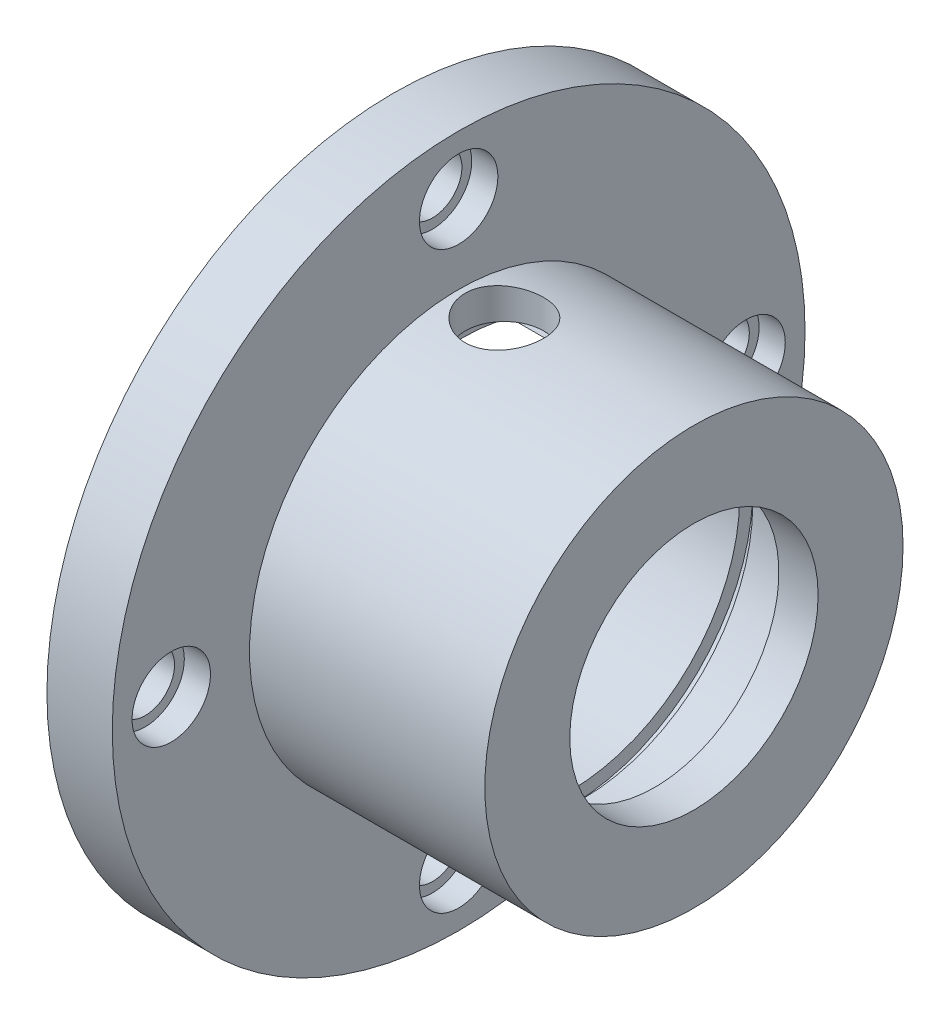
SolidWorks part; units mm, degrees
ref_plane "Front Plane" through (0, 0, 0) normal (0, 0, 1) x (1, 0, 0)
ref_plane "Top Plane" through (0, 0, 0) normal (0, 1, 0) x (1, 0, 0)
ref_plane "Right Plane" through (0, 0, 0) normal (1, 0, 0) x (0, 0, -1)
sketch "Sketch1" plane through (0, 0, 0) normal (1, 0, 0) x (0, 0, -1)
  circle A0 centre (0, 0) radius 26.5
  circle A2 centre (0, -21.9877) radius 2.25
  circle A3 centre (-21.9877, 0) radius 2.25
  circle A4 centre (0, 21.9877) radius 2.25
  circle A5 centre (21.9877, 0) radius 2.25
  point P14 (0, 0)
  dimension "D1" = 53
  dimension "D2" = 4
  dimension "D3" = 4.5
extrude "Boss-Extrude1" add sketch "Sketch1" along normal mid plane 23
sketch "Sketch2" plane through (11.5, 0, 0) normal (1, 0, 0) x (0, 0, -1)
  circle A0 centre (0, 0) radius 16
  circle A1 centre (0, 0) radius 26.5
  circle M3 centre (0, 21.9877) radius 2.25
  circle M4 centre (0, -21.9877) radius 2.25
  circle M5 centre (0, 0) radius 26.5
  circle M6 centre (-21.9877, 0) radius 2.25
  circle M7 centre (21.9877, 0) radius 2.25
  dimension "D1" = 53
  dimension "D3" = 32
extrude "Cut-Extrude1" cut sketch "Sketch2" against normal blind 18 contours A0 M5 M4 M6 M7 M3 region at (11.5, 0, 25.7505)
sketch "Sketch3" plane through (-11.5, 0, 0) normal (-1, 0, 0) x (0, 0, 1)
  circle A0 centre (0, 0) radius 13
  dimension "D1" = 26
extrude "Cut-Extrude2" cut sketch "Sketch3" against normal blind 20
sketch "Sketch4" plane through (8.5, 0, 0) normal (-1, 0, 0) x (0, 0, 1)
  circle A0 centre (0, 0) radius 9.5
  dimension "D1" = 19
extrude "Cut-Extrude3" cut sketch "Sketch4" against normal blind 20
ref_plane "Plane1" through (2.5, 0, 0) normal (-1, 0, 0) x (0, 0, 1)
sketch "Sketch5" plane through (2.5, 0, 0) normal (-1, 0, 0) x (0, 0, 1)
  circle A0 centre (0, 0) radius 14
  dimension "D1" = 28
extrude "Cut-Extrude4" cut sketch "Sketch5" against normal mid plane 1
ref_axis "Axis1" through (26.7383, 0, 0) along (-1, 0, 0)
sketch "Sketch6" plane through (0, 0, 0) normal (0, 1, 0) x (1, 0, 0)
  line L0 (26.7383, 0) -> (-32.37, 0) construction
  line L1 (11.5, -16) -> (11.5, 16) construction
  circle A0 centre (-3, 0) radius 3
  dimension "D1" = 14.5
extrude "Cut-Extrude5" cut sketch "Sketch6" along normal blind 33
ref_plane "Plane3" through (0, 13.5, 0) normal (0, 1, 0) x (1, 0, 0)
sketch "Sketch8" plane through (0, 13.5, 0) normal (0, 1, 0) x (1, 0, 0)
  line L1 (0.1411, -6) -> (-6.1411, -6)
  line L2 (0.1411, -6) -> (0.1411, 6)
  line L3 (0.1411, 6) -> (-6.1411, 6)
  line L4 (-6.1411, -6) -> (-6.1411, 6)
  line L5 (0.1411, -6) -> (-6.1411, 6) construction
  line L6 (0.1411, 6) -> (-6.1411, -6) construction
  point P0 (-3, 0)
  dimension "D1" = 12
extrude "Cut-Extrude6" cut sketch "Sketch8" against normal blind 1
sketch "Sketch9" plane through (-6.5, 0, 0) normal (1, 0, 0) x (0, 0, -1)
  circle A0 centre (0, 21.9877) radius 3
  circle A1 centre (21.9877, 0) radius 3
  circle A2 centre (0, -21.9877) radius 3
  circle A3 centre (-21.9877, 0) radius 3
  point P12 (0, 0)
  dimension "D1" = 4
extrude "Cut-Extrude7" cut sketch "Sketch9" against normal blind 2
